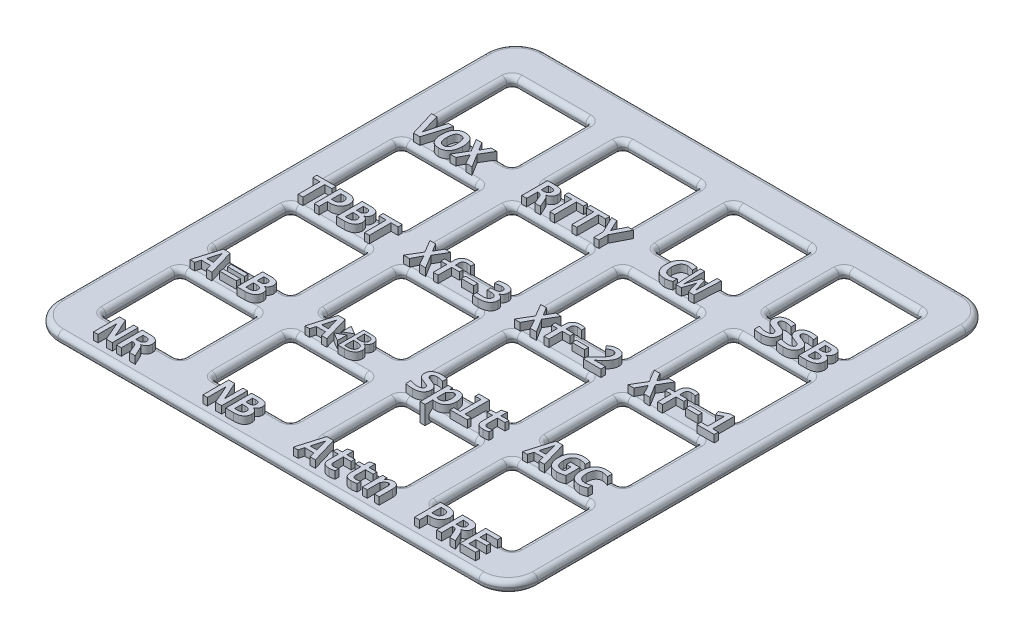
SolidWorks part; units mm, degrees
ref_plane "Front" through (0, 0, 0) normal (0, 0, 1) x (1, 0, 0)
ref_plane "Top" through (0, 0, 0) normal (0, 1, 0) x (1, 0, 0)
ref_plane "Right" through (0, 0, 0) normal (1, 0, 0) x (0, 0, -1)
sketch "Sketch1" plane through (0, 0, 0) normal (0, 1, 0) x (1, 0, 0)
  line L1 (-14.8807, -14.5355) -> (42.1193, -14.5355)
  line L2 (-18.8807, -18.5355) -> (-18.8807, -76.5355)
  line L3 (-14.8807, -80.5355) -> (42.1193, -80.5355)
  line L4 (46.1193, -18.5355) -> (46.1193, -76.5355)
  arc A0 (-14.8807, -14.5355) -> (-18.8807, -18.5355) centre (-14.8807, -18.5355) ccw
  arc A1 (46.1193, -18.5355) -> (42.1193, -14.5355) centre (42.1193, -18.5355) ccw
  arc A2 (42.1193, -80.5355) -> (46.1193, -76.5355) centre (42.1193, -76.5355) ccw
  arc A3 (-18.8807, -76.5355) -> (-14.8807, -80.5355) centre (-14.8807, -76.5355) ccw
  dimension "D1" = 65
  dimension "D2" = 66
extrude "main" add sketch "Sketch1" along normal blind 1.5
sketch "Sketch2" plane through (0, 1.5, 0) normal (0, 1, 0) x (1, 0, 0)
  line L0 (42.1193, -14.5355) -> (-14.8807, -14.5355) construction
  line L1 (-14.2307, -19.6855) -> (-3.5307, -19.6855)
  line L2 (-14.2307, -19.6855) -> (-14.2307, -30.3855)
  line L3 (-14.2307, -30.3855) -> (-3.5307, -30.3855)
  line L4 (-3.5307, -19.6855) -> (-3.5307, -30.3855)
  line L5 (-18.8807, -18.5355) -> (-18.8807, -76.5355) construction
  point P4 (-8.8807, -19.6855)
  dimension "D1" = 5.15
  dimension "D2" = 4.65
  dimension "D3" = 10.7
  dimension "D4" = 10.7
extrude "button hole 1" cut sketch "Sketch2" against normal through all
fillet "button fillet" radius 0.7 12 edges at (-8.8807, 0, 30.3855) (-8.8807, 1.5, 30.3855) (-8.8807, 0, 19.6855) (-8.8807, 1.5, 19.6855) (-3.5307, 0.75, 30.3855) (-3.5307, 0, 25.0355) (-3.5307, 0.75, 19.6855) (-3.5307, 1.5, 25.0355) (-14.2307, 0.75, 19.6855) (-14.2307, 0, 25.0355) (-14.2307, 0.75, 30.3855) (-14.2307, 1.5, 25.0355)
pattern_linear "buttons by 16" count 4 spacing 15 along (1, 0, 0) count 4 spacing 15 along (0, 0, 1) of "button fillet", "button hole 1"
fillet "outer edge fillet" radius 0.7 16 edges at (13.6193, 1.5, 14.5355) (13.6193, 0, 14.5355) (46.1193, 1.5, 47.5355) (46.1193, 0, 47.5355) (13.6193, 1.5, 80.5355) (13.6193, 0, 80.5355) (-18.8807, 1.5, 47.5355) (-18.8807, 0, 47.5355) (44.9477, 1.5, 15.7071) (44.9477, 1.5, 79.364) (-17.7092, 1.5, 79.364) (-17.7092, 1.5, 15.7071) (44.9477, 0, 15.7071) (44.9477, 0, 79.364) (-17.7092, 0, 79.364) (-17.7092, 0, 15.7071)
sketch "Lettering" plane through (0, 0, 0) normal (0, 1, 0) x (1, 0, 0)
  line L0 (45.4193, -49.1355) -> (-18.1807, -49.1355) construction
  line L1 (45.4783, -79.1355) -> (-16.5217, -79.1355) construction
  line L2 (45.4193, -76.5355) -> (45.4193, -18.5355) construction
  line L3 (-18.1807, -18.5355) -> (-18.1807, -76.5355) construction
  line L5 (45.4193, -64.1355) -> (-18.1807, -64.1355) construction
  line L6 (45.4193, -76.5355) -> (45.4193, -18.5355) construction
  line L7 (-18.1807, -18.5355) -> (-18.1807, -76.5355) construction
  line L8 (45.4193, -34.1355) -> (-18.1807, -34.1355) construction
  line L11 (-14.8807, -80.5355) -> (42.1193, -80.5355) construction
  line L16 (6.45, -61.6855) -> (5.3241, -61.0355)
  line L17 (5.3241, -61.0355) -> (5.3241, -62.3355)
  line L18 (5.3241, -62.3355) -> (6.45, -61.6855)
  line L19 (4.9405, -62.9814) -> (6.0628, -63.6376)
  line L20 (6.0628, -63.6376) -> (6.07, -62.3376)
  line L21 (6.07, -62.3376) -> (4.9405, -62.9814)
  line L26 (1.4693, -63.9855) -> (10.7693, -63.9855) construction
  circle A1 centre (5.6994, -61.6855) radius 0.3753 construction
  circle A2 centre (5.6911, -62.9855) radius 0.3753 construction
  text T0 "SSB" font "Consolas" height 3.5
  text T1 "CW" font "Consolas" height 3.5
  text T2 "RTTY" font "Consolas" height 3.5
  text T3 "VOX" font "Consolas" height 3.5
  text T4 "AGC" font "Consolas" height 3.5
  text T5 "Splt" font "Consolas" height 3.5
  text T6 "PRE" font "Consolas" height 3.5
  text T7 "A" font "Consolas" height 3.5
  text T8 "TPBT" font "Consolas" height 3.5
  text T9 "Attn" font "Consolas" height 3.5
  text T10 "NB" font "Consolas" height 3.5
  text T11 "NR" font "Consolas" height 3.5
  text T12 "Xf-1" font "Consolas" height 3.5
  text T13 "Xf-2" font "Consolas" height 3.5
  text T14 "Xf-3" font "Consolas" height 3.5
  text T15 "A=B" font "Consolas" height 3.5
  text T17 "B" font "Consolas" height 3.5
  point P33 (0, 0)
  point P34 (0, 0)
  point P35 (0, 0)
  point P37 (-14.1299, -34.1202)
  point P38 (16.2896, -64.1355)
  point P43 (0, 0)
  point P45 (15.8388, -64.1355)
  point P51 (0, 0)
  point P52 (0, 0)
  point P54 (0, 0)
  point P55 (0, 0)
  point P56 (0, 0)
  point P57 (0, 0)
  point P58 (15.4915, -64.1355)
  dimension "D1" = 46.4
  dimension "D2" = 16.4
  dimension "D3" = 1.4
  dimension "D4" = 31.4
  dimension "D5" = 1.3
  dimension "D6" = 1.3
  dimension "D7" = 1
extrude "lettering boss" add sketch "Lettering" along normal blind 2.5
